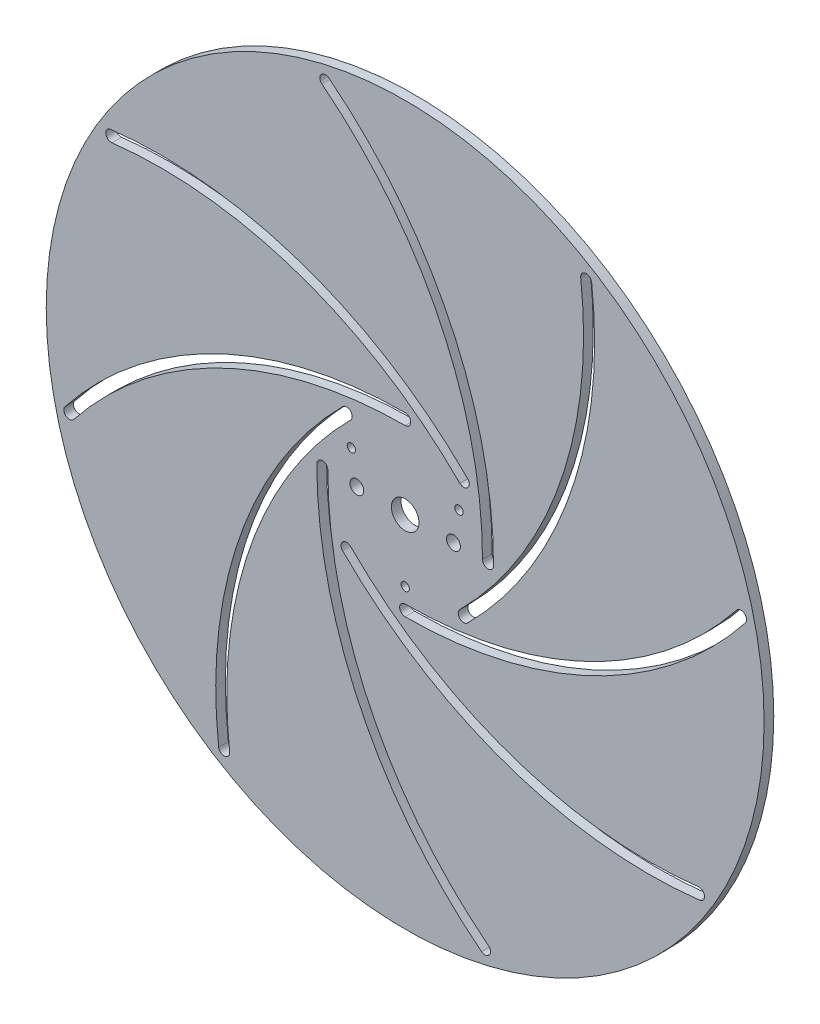
SolidWorks part; units mm, degrees
ref_plane "Front Plane" through (0, 0, 0) normal (0, 0, 1) x (1, 0, 0)
ref_plane "Top Plane" through (0, 0, 0) normal (0, 1, 0) x (1, 0, 0)
ref_plane "Right Plane" through (0, 0, 0) normal (1, 0, 0) x (0, 0, -1)
sketch "Sketch1" plane through (0, 0, 0) normal (0, 0, 1) x (1, 0, 0)
  line L0 (30, 0) -> (-130, 0) construction
  line L1 (0, 30) -> (0, -125) construction
  circle A0 centre (0, 0) radius 130
  circle A2 centre (0, 0) radius 30 construction
  circle A3 centre (0, 0) radius 125 construction
  arc A4 (0, 30) -> (-121.6133, -28.9) centre (0, -125) ccw construction
  arc A5 (0, 32) -> (-123.1825, -27.66) centre (0, -125) ccw
  arc A6 (0, 28) -> (-120.0441, -30.14) centre (0, -125) ccw
  arc A7 (0, 28) -> (0, 32) centre (0, 30) ccw
  arc A8 (-123.1825, -27.66) -> (-120.0441, -30.14) centre (-121.6133, -28.9) ccw
  arc A9 (21.2132, 21.2132) -> (-106.429, 65.5582) centre (-88.3883, -88.3883) ccw construction
  arc A14 (22.6274, 22.6274) -> (-106.6617, 67.5446) centre (-88.3883, -88.3883) ccw
  arc A19 (19.799, 19.799) -> (-106.1962, 63.5718) centre (-88.3883, -88.3883) ccw
  arc A24 (19.799, 19.799) -> (22.6274, 22.6274) centre (21.2132, 21.2132) ccw
  arc A29 (-106.6617, 67.5446) -> (-106.1962, 63.5718) centre (-106.429, 65.5582) ccw
  arc A35 (30, 0) -> (-28.9, 121.6133) centre (-125, 0) ccw construction
  arc A36 (32, 0) -> (-27.66, 123.1825) centre (-125, 0) ccw
  arc A37 (28, 0) -> (-30.14, 120.0441) centre (-125, 0) ccw
  arc A38 (28, 0) -> (32, 0) centre (30, 0) ccw
  arc A39 (-27.66, 123.1825) -> (-30.14, 120.0441) centre (-28.9, 121.6133) ccw
  arc A40 (21.2132, -21.2132) -> (65.5582, 106.429) centre (-88.3883, 88.3883) ccw construction
  arc A41 (22.6274, -22.6274) -> (67.5446, 106.6617) centre (-88.3883, 88.3883) ccw
  arc A42 (19.799, -19.799) -> (63.5718, 106.1962) centre (-88.3883, 88.3883) ccw
  arc A43 (19.799, -19.799) -> (22.6274, -22.6274) centre (21.2132, -21.2132) ccw
  arc A44 (67.5446, 106.6617) -> (63.5718, 106.1962) centre (65.5582, 106.429) ccw
  arc A45 (0, -30) -> (121.6133, 28.9) centre (0, 125) ccw construction
  arc A46 (0, -32) -> (123.1825, 27.66) centre (0, 125) ccw
  arc A47 (0, -28) -> (120.0441, 30.14) centre (0, 125) ccw
  arc A48 (0, -28) -> (0, -32) centre (0, -30) ccw
  arc A49 (123.1825, 27.66) -> (120.0441, 30.14) centre (121.6133, 28.9) ccw
  arc A50 (-21.2132, -21.2132) -> (106.429, -65.5582) centre (88.3883, 88.3883) ccw construction
  arc A51 (-22.6274, -22.6274) -> (106.6617, -67.5446) centre (88.3883, 88.3883) ccw
  arc A52 (-19.799, -19.799) -> (106.1962, -63.5718) centre (88.3883, 88.3883) ccw
  arc A53 (-19.799, -19.799) -> (-22.6274, -22.6274) centre (-21.2132, -21.2132) ccw
  arc A54 (106.6617, -67.5446) -> (106.1962, -63.5718) centre (106.429, -65.5582) ccw
  arc A55 (-30, 0) -> (28.9, -121.6133) centre (125, 0) ccw construction
  arc A56 (-32, 0) -> (27.66, -123.1825) centre (125, 0) ccw
  arc A57 (-28, 0) -> (30.14, -120.0441) centre (125, 0) ccw
  arc A58 (-28, 0) -> (-32, 0) centre (-30, 0) ccw
  arc A59 (27.66, -123.1825) -> (30.14, -120.0441) centre (28.9, -121.6133) ccw
  arc A60 (-21.2132, 21.2132) -> (-65.5582, -106.429) centre (88.3883, -88.3883) ccw construction
  arc A61 (-22.6274, 22.6274) -> (-67.5446, -106.6617) centre (88.3883, -88.3883) ccw
  arc A62 (-19.799, 19.799) -> (-63.5718, -106.1962) centre (88.3883, -88.3883) ccw
  arc A63 (-19.799, 19.799) -> (-22.6274, 22.6274) centre (-21.2132, 21.2132) ccw
  arc A64 (-67.5446, -106.6617) -> (-63.5718, -106.1962) centre (-65.5582, -106.429) ccw
  circle A65 centre (0, 0) radius 5
  circle A66 centre (-17.5, 0) radius 2.5
  arc A67 (-0.5, 4.9749) -> (0.5556, 4.969) centre (0, 0) cw
  circle A73 centre (0, 0) radius 17.5 construction
  circle A80 centre (17.5, 0) radius 2.5
  circle A81 centre (0, 0) radius 22.5 construction
  circle A84 centre (0, -22.5) radius 1.5
  circle A85 centre (-19.4856, 11.25) radius 1.5
  circle A86 centre (19.4856, 11.25) radius 1.5
  point P11 (-67.5629, 14.5)
  point P22 (-37.5212, 58.0273)
  point P30 (14.5, 67.5629)
  point P38 (58.0273, 37.5212)
  point P46 (67.5629, -14.5)
  point P54 (37.5212, -58.0273)
  point P59 (-0.3062, 0.1031)
  point P63 (-14.5, -67.5629)
  point P71 (-58.0273, -37.5212)
  point P76 (0, 0)
  point P78 (0, 0)
  point P89 (0, 0)
  point P93 (0, 0)
  point P101 (0, 0)
  point P102 (0, 0)
  point P104 (0, 0)
  dimension "D2" = 260
  dimension "D3" = 250
  dimension "D4" = 60
  dimension "D5" = 4
  dimension "D6" = 2
  dimension "D8" = 10
  dimension "D11" = 3
  dimension "D12" = 5
  dimension "D14" = 35
  dimension "D9" = 45
  dimension "D10" = 3
  dimension "D7" = 8
extrude "Boss-Extrude1" add sketch "Sketch1" along normal blind 1.75 and the other way blind 1.75 contours A0 A54 A51 A53 A52 A49 A46 A48 A47 A8 A5 A7 A6 | A65 region at (-126.323, 0, 0)
